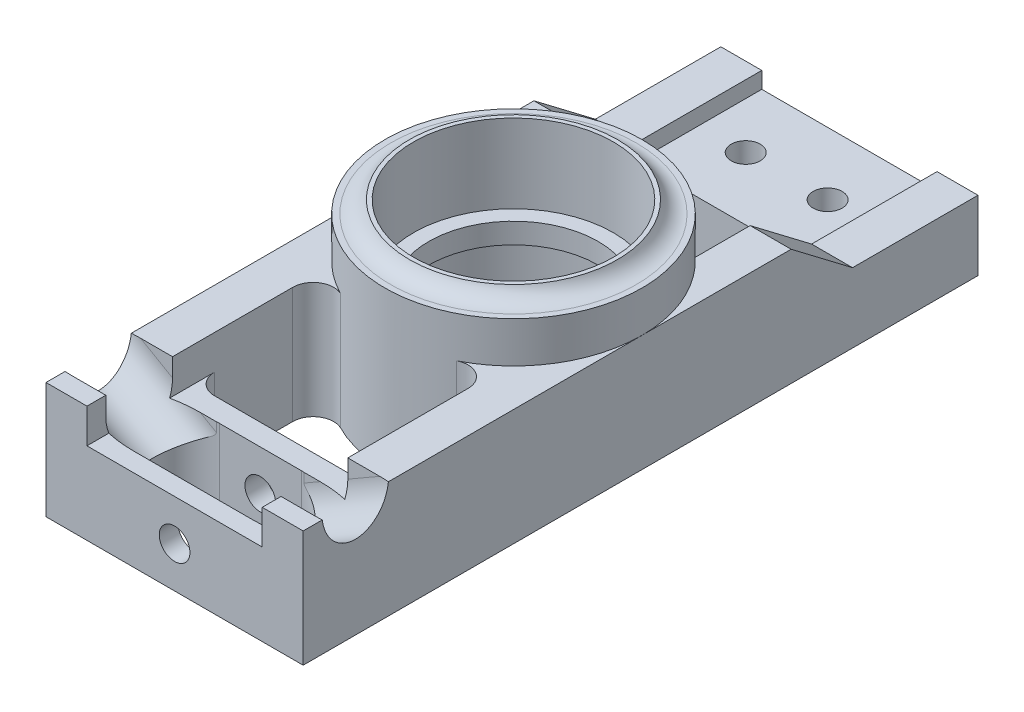
SolidWorks part; units mm, degrees
material "6061-T6 (SS)"
ref_plane "Front Plane" through (0, 0, 0) normal (0, 0, 1) x (1, 0, 0)
ref_plane "Top Plane" through (0, 0, 0) normal (0, 1, 0) x (1, 0, 0)
ref_plane "Right Plane" through (0, 0, 0) normal (1, 0, 0) x (0, 0, -1)
sketch "Bearing Sketch" plane through (0, 0, 0) normal (1, 0, 0) x (0, 0, -1)
  line L0 (0, 0) -> (0, 16.3466) construction
  line L1 (4.8872, 0) -> (-19.6002, 0) construction
  line L2 (-39.878, 0) -> (-39.878, 48.768)
  line L3 (-39.878, 48.768) -> (-32.258, 48.768)
  line L4 (-32.258, 48.768) -> (-32.258, 52.578)
  line L5 (-32.258, 52.578) -> (-30.9994, 52.578)
  line L6 (-30.9994, 52.578) -> (-30.9994, 28.194)
  line L7 (-30.9994, 28.194) -> (-26.289, 28.194)
  line L8 (-26.289, 28.194) -> (-26.289, 21.844)
  line L9 (-26.289, 21.844) -> (-30.9994, 21.844)
  line L10 (-30.9994, 21.844) -> (-30.9994, 0)
  line L11 (-30.9994, 0) -> (-39.878, 0)
  point P2 (-32.258, 50.673)
  dimension "D1" = 61.9989
  dimension "D2" = 61.9989
  dimension "D3" = 6.35
  dimension "D4" = 48.768
  dimension "D5" = 64.516
  dimension "D6" = 79.756
  dimension "D7" = 24.384
  dimension "D8" = 21.844
  dimension "D9" = 52.578
revolve "Bearing Revolve" add sketch "Bearing Sketch" angle 360 about L0
fillet "Housing Fillet Lip" radius 6.35 1 edges at (0, 48.768, -32.258)
sketch "PrepArea(WithadjWidth)" plane through (0, 0, 0) normal (0, 1, 0) x (1, 0, 0)
  line L2 (0, 0) -> (0, 15.1173) construction
  line L3 (-39.878, 0) -> (-39.878, 46.228)
  line L4 (-39.878, 46.228) -> (39.878, 46.228)
  line L5 (39.878, 46.228) -> (39.878, 0)
  circle A2 centre (0, 0) radius 39.878 construction
  arc A3 (-39.878, 0) -> (39.878, 0) centre (0, 0) cw
  dimension "D2" = 6.35
extrude "UBJ Material Prep" add sketch "PrepArea(WithadjWidth)" along normal offset from surface (36.068 mm away) 12.7 up to face at (0, 48.768, -38.0779)
sketch "Sketch27" plane through (-39.878, 0, 0) normal (-1, 0, 0) x (0, 0, 1)
  line L0 (-46.228, 36.068) -> (-65.278, 21.59)
  line L1 (-65.278, 21.59) -> (-104.1908, 21.59)
  line L5 (-46.228, 0) -> (-46.228, 36.068)
  line L6 (-104.1908, 21.59) -> (-104.1908, 0)
  line L7 (-104.1908, 0) -> (-91.9595, 0)
  line L8 (-200004.8872, 0) -> (200019.6002, 0) construction
  line L9 (-91.9595, 0) -> (-46.228, 0)
  line L10 (0, 12.7) -> (63.9876, 12.7) construction
  line L11 (0, -200000) -> (0, 200016.3466) construction
  line L12 (-84.7344, 21.59) -> (-84.7344, 12.7) construction
  dimension "D6" = 12.7
  dimension "D4" = 84.7344
  dimension "D5" = 8.89
  dimension "D2" = 90
  dimension "D1" = 19.05
extrude "UBJ Arm TK" add sketch "Sketch27" against normal up to surface (79.756 mm away) up to face at (39.878, 18.034, -23.114)
sketch "Sketch32" plane through (0, 21.59, 0) normal (0, 1, 0) x (1, 0, 0)
  line L0 (0, 104.1908) -> (0, 65.278) construction
  line L2 (39.878, 104.1908) -> (-39.878, 104.1908) construction
  line L3 (39.878, 65.278) -> (-39.878, 65.278) construction
  line L4 (0, 84.7344) -> (-12.7, 84.7344) construction
  circle A0 centre (-12.7, 84.7344) radius 4.5
  circle A1 centre (12.7, 84.7344) radius 4.5
  dimension "D1" = 9
  dimension "D2" = 9
  dimension "D3" = 12.7
  dimension "D4" = 25.4
extrude "CamberBlock Holes " cut sketch "Sketch32" against normal up to surface (21.59 mm away) up to face at (0, 0, -30.9994)
sketch "Sketch28" plane through (0, 21.59, 0) normal (0, 1, 0) x (1, 0, 0)
  line L0 (0, 200004.8872) -> (0, -200019.6002) construction
  line L1 (-27.178, 65.278) -> (27.178, 65.278)
  line L2 (-27.178, 65.278) -> (-27.178, 104.1908)
  line L3 (-27.178, 104.1908) -> (27.178, 104.1908)
  line L4 (27.178, 65.278) -> (27.178, 104.1908)
  line L5 (-27.178, 65.278) -> (27.178, 104.1908) construction
  line L6 (-27.178, 104.1908) -> (27.178, 65.278) construction
  line L7 (39.878, 104.1908) -> (-39.878, 104.1908) construction
  line L8 (-39.878, 65.278) -> (-39.878, 104.1908) construction
  line L9 (39.878, 65.278) -> (-39.878, 65.278) construction
  point P0 (0, 84.7344)
  dimension "D1" = 12.7
extrude "UBJ Cross Member TK" cut sketch "Sketch28" against normal blind 5.08
sketch "Sketch30" plane through (0, 36.068, 0) normal (0, 1, 0) x (1, 0, 0)
  line L1 (-27.178, 65.278) -> (27.178, 65.278)
  line L2 (-27.178, 65.278) -> (-27.178, 29.1824)
  line L4 (27.178, 65.278) -> (27.178, 29.1824)
  line L5 (27.178, 65.278) -> (27.178, 104.1908) construction
  arc A0 (39.878, 0) -> (-39.878, 0) centre (0, 0) ccw construction
  arc A1 (-27.178, 29.1824) -> (27.178, 29.1824) centre (0, 0) cw
extrude "UBJ Mass Cutting" cut sketch "Sketch30" against normal up to surface (36.068 mm away)
sketch "Sketch9" plane through (0, 0, 0) normal (0, -1, 0) x (1, 0, 0)
  line L0 (-39.878, 0) -> (-39.878, 105.0925)
  line L1 (-39.878, 105.0925) -> (39.878, 105.0925)
  line L2 (39.878, 105.0925) -> (39.878, 0)
  line L3 (-39.878, -104.1908) -> (-39.878, 0) construction
  line L4 (-12.7, 88.9) -> (12.7, 88.9) construction
  line L5 (0, -200004.8872) -> (0, 200019.6002) construction
  line L6 (-12.7, 99.2505) -> (12.7, 99.2505) construction
  line L7 (-12.7, 78.5495) -> (12.7, 78.5495) construction
  arc A0 (-12.7, 99.2505) -> (-12.7, 78.5495) centre (-12.7, 88.9) ccw construction
  arc A2 (39.878, 0) -> (-39.878, 0) centre (0, 0) ccw construction
  arc A3 (-39.878, 0) -> (39.878, 0) centre (0, 0) cw
  arc A4 (12.7, 78.5495) -> (12.7, 99.2505) centre (12.7, 88.9) ccw construction
  point P13 (0, 88.9)
  dimension "D2" = 25.4
  dimension "D3" = 20.701
  dimension "D4" = 5.842
  dimension "D1" = 88.9
extrude "LBJ Material Prep" add sketch "Sketch9" against normal offset from surface (36.068 mm away) 12.7 up to face at (0, 48.768, -38.0779)
sketch "Sketch10" plane through (0, 36.068, 0) normal (0, 1, 0) x (1, 0, 0)
  line L0 (-27.178, -29.1824) -> (-27.178, -105.0925)
  line L1 (-39.878, -105.0925) -> (39.878, -105.0925) construction
  line L2 (27.178, -29.1824) -> (27.178, -105.0925)
  line L3 (-39.878, 0) -> (-39.878, -105.0925) construction
  line L4 (39.878, -105.0925) -> (39.878, 0) construction
  line L5 (-27.178, -105.0925) -> (27.178, -105.0925)
  circle A0 centre (0, 0) radius 39.878 construction
  arc A1 (-27.178, -29.1824) -> (27.178, -29.1824) centre (0, 0) ccw
  dimension "D1" = 12.7
  dimension "D2" = 12.7
extrude "Flat LBJ Prep" cut sketch "Sketch10" against normal offset from surface (10.668 mm away) 25.4
sketch "Sketch12" plane through (0, 25.4, 0) normal (0, 1, 0) x (1, 0, 0)
  line L0 (-12.7, -88.86) -> (12.7, -88.86) construction
  line L1 (-12.7, -78.5095) -> (12.7, -78.5095)
  line L2 (-12.7, -99.2105) -> (12.7, -99.2105)
  line L3 (27.178, -105.0925) -> (-27.178, -105.0925) construction
  line L4 (0, 0) -> (0, -140.8541) construction
  arc A0 (-12.7, -78.5095) -> (-12.7, -99.2105) centre (-12.7, -88.86) ccw
  arc A1 (12.7, -99.2105) -> (12.7, -78.5095) centre (12.7, -88.86) ccw
  point P2 (0, -88.86)
  dimension "D1" = 20.701
  dimension "D2" = 25.4
  dimension "D3" = 5.882
extrude "LBJ Slot" cut sketch "Sketch12" against normal up to surface (25.4 mm away)
sketch "Sketch13" plane through (0, 25.4, 0) normal (0, 1, 0) x (1, 0, 0)
  line L0 (-27.178, -29.1824) -> (-27.178, -71.8674)
  line L1 (-27.178, -105.0925) -> (-27.178, -29.1824) construction
  line L2 (-27.178, -71.8674) -> (27.178, -71.8674)
  line L3 (27.178, -29.1824) -> (27.178, -105.0925) construction
  line L4 (27.178, -71.8674) -> (27.178, -29.1824)
  line L5 (12.7, -78.5095) -> (-12.7, -78.5095) construction
  arc A0 (-27.178, -29.1824) -> (27.178, -29.1824) centre (0, 0) ccw
  circle A1 centre (0, 0) radius 39.878 construction
  dimension "D1" = 6.6421
extrude "LBJ Weight and Bolt Clearing" cut sketch "Sketch13" against normal up to surface (25.4 mm away)
fillet "LBJ Fillet" radius 6.35 4 edges at (27.178, 12.7, 71.8674) (-27.178, 12.7, 71.8674) (27.178, 18.034, 29.1824) (-27.178, 18.034, 29.1824)
sketch "Sketch14" plane through (0, 0, 105.0925) normal (0, 0, 1) x (1, 0, 0)
  line L2 (0, 0) -> (0, 25.4) construction
  line L3 (27.178, 25.4) -> (-27.178, 25.4) construction
  circle A0 centre (0, 12.7) radius 4.7625
  dimension "D1" = 9.525
extrude "LBJ Hole" cut sketch "Sketch14" against normal up to surface (33.2251 mm away) up to face at (0, 12.7, 71.8674)
sketch "Sketch33" plane through (0, 0, 0) normal (-0.866, 0.5, 0) x (0, 0, 1)
  line L2 (88.9, 0) -> (88.9, 49.7522) construction
  line L4 (88.9, 12.7) -> (88.9, 22.86) construction
  line L5 (78.5495, 12.7) -> (78.5495, 22.86)
  line L6 (99.2505, 12.7) -> (99.2505, 22.86)
  line L7 (-200004.8872, 0) -> (200019.6002, 0) construction
  arc A1 (78.5495, 12.7) -> (99.2505, 12.7) centre (88.9, 12.7) ccw
  arc A2 (99.2505, 22.86) -> (78.5495, 22.86) centre (88.9, 22.86) ccw
  point P4 (88.9, 17.78)
  dimension "D1" = 88.9
  dimension "D2" = 20.701
  dimension "D3" = 12.7
  dimension "D4" = 10.16
ref_plane "Mouth_cut Plane" through (0, 0, 0) normal (-0.866, 0.5, 0) x (0, 0, 1)
extrude "Mouth Widen" cut sketch "Sketch33" along normal through all
mirror "Mouth Mirror" about plane through (0, 0, 0) normal (1, 0, 0) of "Mouth Widen"
ref_plane "Brake Caliper Face" through (0, 20.17, 0) normal (0, -1, 0) x (-1, 0, 0)
equation "\"KPI\"= 12'CRIT Malleable-WIll fill in from Sus"
equation "\"Bearing_Inner_Boar\"= 1.25in"
equation "\"Bearing_Outer_Bore\"= 2.4409in'Static-Press Fit Bearing"
equation "\"Bearing_Thickness\"= .7150in"
equation "\"D1@Bearing Sketch\"=\"Bearing_Outer_Bore\""
equation "\"D2@Bearing Sketch\"=\"Bearing_Outer_Bore\""
equation "\"UBJ_angle\"= 81'Malleable-Only change for clearance"
equation "\"UBJ_Distance\"= 3.336in'New"
equation "\"D4@Sketch27\"=\"UBJ_Distance\""
equation "\"LBJ_Distance\"= 3.5'Malleable-Will change for KPI (but will mostly stay put and it will move for clearnance"
equation "\"D1@Sketch9\"=\"LBJ_Distance\""
equation "\"Dist_Hub_to_Rear_Upright\"= 1.281in'New-Dist From Rim Face to Rear Upright"
equation "\"Wheel_Offset\"= 22mm'Static-Distance from Rim mount to center"
equation "\"Camber_Block_Distance\"= 2.286'Static-BUT-Camber Block From rear to center of holes BUT not referenced"
equation "\"UBJ_Depth\"= 0.2in'Malleable-May change_ Depth that the camber block is resessed"
equation "\"D1@UBJ Cross Member TK\"= \"UBJ_Depth\""
equation "\"UBJ_Jut_Out\"= \"Camber_Block_Distance\" + .35in - \"UBJ_Depth\""
equation "\"Vert_UBJtoLBJ_Dist\"= \"Y\" + \"Z\"'Output-This seems wrong"
equation "\"Y\"= cos ( \"UBJ_angle\" ) * \"UBJ_Jut_Out\"'inbetwen"
equation "\"Z\"= sin ( \"UBJ_angle\" ) * \"UBJ_Jut_Out\" / tan ( \"KPI\" + \"Static_Camber\" ) * 1in'inbetween-CHECK I don't trust Static Camber"
equation "\"Static_Camber\"= - 2'CRIT Malleable-Will Fill in From Sus"
equation "\"D1@Sketch33\"=\"LBJ_Distance\""
equation "\"FillerDIVIDER\"= 0.000000000'(Just for clarity)"
equation "\"Test_UBJ\" = \"UBJ_Distance\" + 2"
